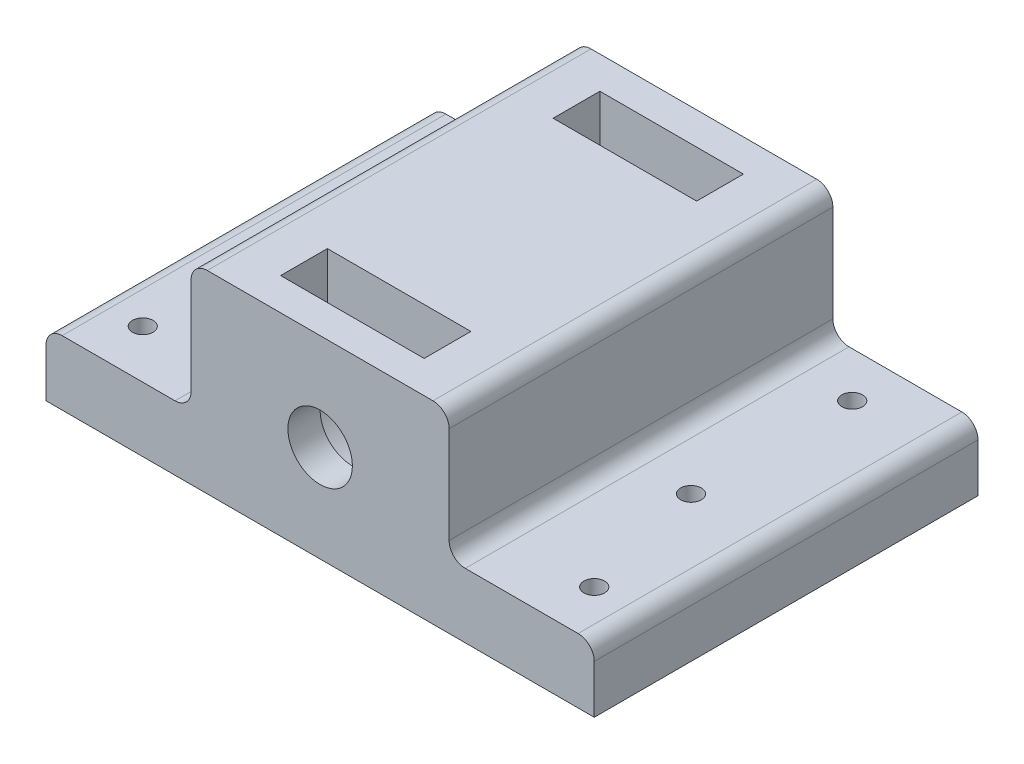
SolidWorks part; units mm, degrees
ref_plane "Front Plane" through (0, 0, 0) normal (0, 0, 1) x (1, 0, 0)
ref_plane "Top Plane" through (0, 0, 0) normal (0, 1, 0) x (1, 0, 0)
ref_plane "Right Plane" through (0, 0, 0) normal (1, 0, 0) x (0, 0, -1)
sketch "Sketch2" plane through (0, 0, 0) normal (0, 0, 1) x (1, 0, 0)
  line L0 (0, 30) -> (85, 0) construction
  line L1 (0, 0) -> (85, 0)
  line L2 (0, 0) -> (0, 30)
  line L3 (0, 30) -> (85, 30)
  line L4 (85, 0) -> (85, 30)
  line L5 (42.5, 30) -> (42.5, 15) construction
  line L6 (62.5, 30) -> (85, 30)
  line L7 (62.5, 30) -> (62.5, 10)
  line L8 (62.5, 10) -> (85, 10)
  line L9 (85, 30) -> (85, 10)
  line L10 (22.5, 10) -> (0, 10)
  line L11 (22.5, 30) -> (22.5, 10)
  circle A0 centre (42.5, 15) radius 5
  dimension "D3" = 10
  dimension "D1" = 30
  dimension "D2" = 85
  dimension "D4" = 20
  dimension "D5" = 22.5
extrude "Boss-Extrude1" add sketch "Sketch2" along normal blind 15 and the other way blind 44.5 contours L3 L11 L10 L2 L1 L4 L8 L7 A0 region at (0.9014, 5, 0)
sketch "Sketch3" plane through (0, 0, 0) normal (0, 1, 0) x (1, 0, 0)
  line L0 (0, -7.5) -> (85, -7.5) construction
  line L2 (22.5, 44.5) -> (62.5, 44.5) construction
  line L3 (42.5, 44.5) -> (42.5, -15) construction
  line L10 (0, 44.5) -> (0, -15) construction
  line L11 (85, 44.5) -> (85, -15) construction
  line L12 (22.5, -15) -> (62.5, -15) construction
  circle A0 centre (7.5, -7.5) radius 1.6
  circle A1 centre (77.5, -7.5) radius 1.6
  circle A2 centre (72.5, 12.5) radius 1.6
  circle A3 centre (12.5, 12.5) radius 1.6
  circle A4 centre (72.5, 37.5) radius 1.6
  circle A5 centre (12.5, 37.5) radius 1.6
  dimension "D1" = 3.2
  dimension "D3" = 3.2
  dimension "D4" = 20
  dimension "D6" = 7.5
  dimension "D7" = 25
  dimension "D2" = 70
  dimension "D5" = 30
extrude "Cut-Extrude1" cut sketch "Sketch3" along normal through all both and the other way through all contours A2 | A3 | A0 | A1 | A5 | A4 region at (7.5, 0, 7.5) region at (77.5, 0, 7.5) region at (72.5, 0, -12.5) region at (12.5, 0, -12.5) region at (72.5, 0, -37.5) region at (12.5, 0, -37.5)
fillet "Fillet1" radius 2.5 6 edges at (62.5, 10, -14.75) (22.5, 10, -14.75) (85, 10, -14.75) (0, 10, -14.75) (62.5, 30, -14.75) (22.5, 30, -14.75)
ref_plane "Plane1" through (0, 0, 10) normal (0, 0, 1) x (1, 0, 0)
sketch "Sketch5" plane through (0, 0, 0) normal (0, 0, 1) x (1, 0, 0)
  line L0 (42.5, 15) -> (42.5, 30) construction
  line L1 (25, 30) -> (60, 30) construction
  line L3 (31.375, 30) -> (31.375, 15)
  line L4 (31.375, 15) -> (53.625, 15) construction
  line L5 (53.625, 15) -> (53.625, 30)
  line L6 (53.625, 30) -> (31.375, 30)
  arc A0 (53.625, 15) -> (31.375, 15) centre (42.5, 15) cw
  circle A1 centre (42.5, 15) radius 5 construction
  circle A2 centre (42.5, 15) radius 5 construction
  point P5 (42.5, 3.875)
  point P12 (42.5, 15)
  dimension "D1" = 11.125
  dimension "D2" = 22.25
extrude "Cut-Extrude5" cut sketch "Sketch5" against normal blind 7.25 from surface starting at plane "Plane1"
ref_plane "Plane2" through (0, 0, -39.5) normal (0, 0, -1) x (-1, 0, 0)
extrude "Cut-Extrude6" cut sketch "Sketch5<2>" along normal blind 7.25 from surface starting at plane "Plane2"
sketch "Sketch5<2>" plane through (0, 0, 0) normal (0, 0, 1) x (1, 0, 0) same geometry as "Sketch5"
equation "\"bearingthickness\"= 7mm"
equation "\"bearingOD\"= 22mm"
equation "\"D2@Sketch5\"=\"bearingOD\"+0.25mm"
equation "\"D1@Sketch5\"=\"D2@Sketch5\"/2"
equation "\"D1@Cut-Extrude5\"=\"bearingthickness\"+0.25mm"
equation "\"D1@Cut-Extrude6\"=\"bearingthickness\"+0.25mm"
